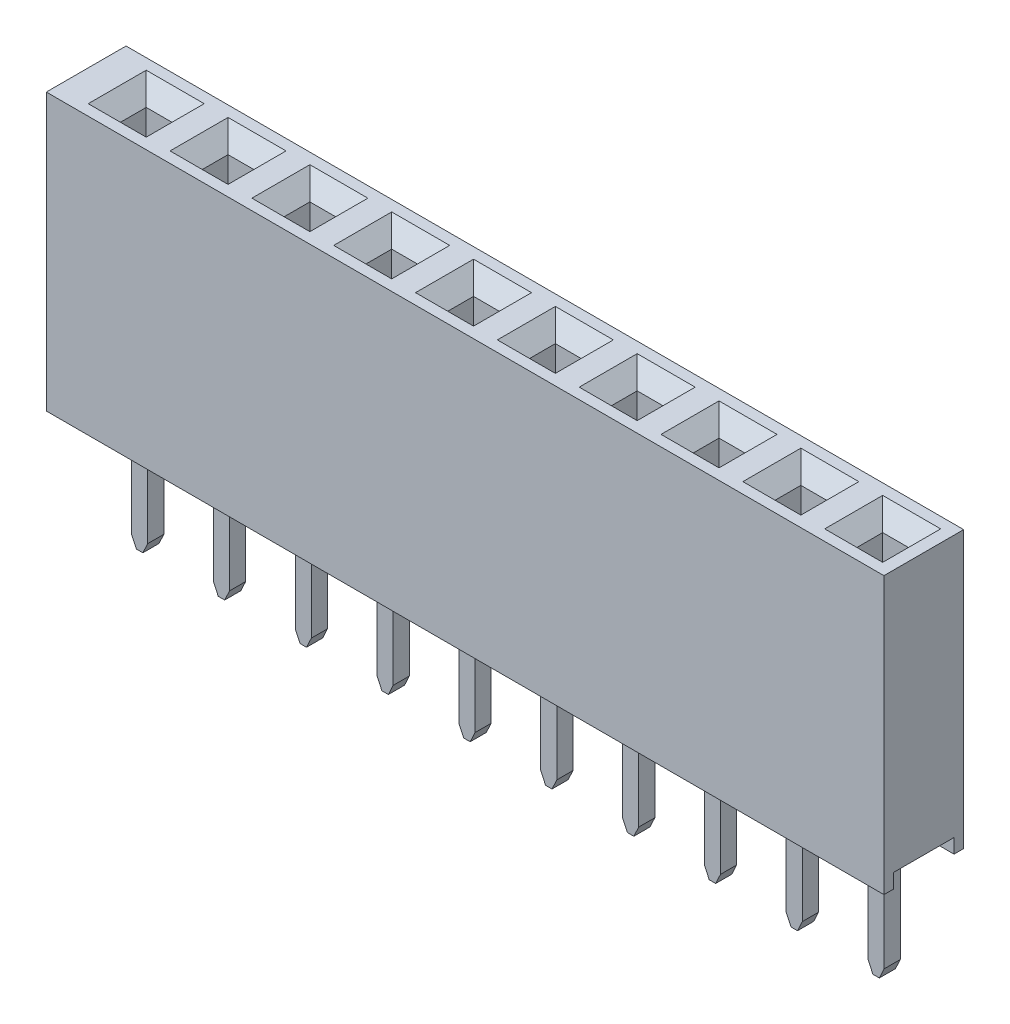
SolidWorks part; units mm, degrees
ref_plane "Front" through (0, 0, 0) normal (0, 0, 1) x (1, 0, 0)
ref_plane "Top" through (0, 0, 0) normal (0, 1, 0) x (1, 0, 0)
ref_plane "Right" through (0, 0, 0) normal (1, 0, 0) x (0, 0, -1)
sketch "Sketch1" plane through (0, 0, 0) normal (0, 0, 1) x (1, 0, 0)
  line L1 (13, -4.2875) -> (-13, -4.2875)
  line L2 (13, -4.2875) -> (13, 4.2875)
  line L3 (13, 4.2875) -> (-13, 4.2875)
  line L4 (-13, -4.2875) -> (-13, 4.2875)
  line L5 (13, -4.2875) -> (-13, 4.2875) construction
  line L6 (13, 4.2875) -> (-13, -4.2875) construction
  point P0 (0, 0)
  dimension "D1" = 26
  dimension "D2" = 8.575
extrude "Boss-Extrude1" add sketch "Sketch1" along normal mid plane 2.475
sketch "Sketch2" plane through (0, 0, 0) normal (1, 0, 0) x (0, 0, -1)
  line L0 (-0.9375, -4.2875) -> (0.9375, -4.2875)
  line L1 (-1.2375, -4.2875) -> (1.2375, -4.2875) construction
  line L2 (0.9375, -4.2875) -> (0.9375, -3.8396)
  line L3 (0.9375, -3.8396) -> (-0.9375, -3.8396)
  line L4 (-0.9375, -3.8396) -> (-0.9375, -4.2875)
  line L5 (1.2375, -4.2875) -> (1.2375, 4.2875) construction
  line L6 (-1.2375, -4.2875) -> (-1.2375, 4.2875) construction
  dimension "D1" = 0.3
  dimension "D2" = 0.3
extrude "Cut-Extrude1" cut sketch "Sketch2" against normal mid plane 100
sketch "Sketch4" plane through (0, 4.2875, 0) normal (0, 1, 0) x (1, 0, 0)
  line L0 (-13, 0) -> (13, 0) construction
  line L1 (-13, -1.2375) -> (-13, 1.2375) construction
  line L2 (13, -1.2375) -> (13, 1.2375) construction
  line L4 (-12.0116, 0.875) -> (-10.2616, 0.875)
  line L5 (-12.0116, 0.875) -> (-12.0116, -0.875)
  line L6 (-12.0116, -0.875) -> (-10.2616, -0.875)
  line L7 (-10.2616, 0.875) -> (-10.2616, -0.875)
  line L8 (-12.0116, 0.875) -> (-10.2616, -0.875) construction
  line L9 (-12.0116, -0.875) -> (-10.2616, 0.875) construction
  line L10 (-11.5366, 0.4) -> (-10.7366, 0.4)
  line L11 (-11.5366, 0.4) -> (-11.5366, -0.4)
  line L12 (-11.5366, -0.4) -> (-10.7366, -0.4)
  line L13 (-10.7366, 0.4) -> (-10.7366, -0.4)
  line L14 (-11.5366, 0.4) -> (-10.7366, -0.4) construction
  line L15 (-11.5366, -0.4) -> (-10.7366, 0.4) construction
  point P6 (-11.1366, 0)
  point P11 (-11.1366, 0)
  dimension "D1" = 1.75
  dimension "D2" = 0.8
extrude "Cut-Extrude2" cut sketch "Sketch4" against normal blind 1.5 contours L13 L10 L11 L12 region at (-11.1366, 4.2875, 0)
chamfer "Chamfer1" distance 0.5 angle 45 4 edges at (-11.1366, 4.2875, -0.4) (-11.5366, 4.2875, 0) (-11.1366, 4.2875, 0.4) (-10.7366, 4.2875, 0)
sketch "Sketch5" plane through (0, 0, 0) normal (0, 1, 0) x (1, 0, 0)
  line L1 (-12.0366, 0.9) -> (-10.2366, 0.9)
  line L2 (-12.0366, 0.9) -> (-12.0366, -0.9)
  line L3 (-12.0366, -0.9) -> (-10.2366, -0.9)
  line L4 (-10.2366, 0.9) -> (-10.2366, -0.9)
extrude "Cut-Extrude3" cut sketch "Sketch5" against normal blind 3 and the other way blind 3
sketch "Sketch9" plane through (0, 0, 0) normal (0, 0, 1) x (1, 0, 0)
  line L0 (-11.0903, 1.6344) -> (-11.0903, -6.2348) construction
  line L1 (-10.2376, -1.308) -> (-10.4881, -1.2272)
  line L2 (-10.4881, -1.2272) -> (-10.677, 1.5255)
  line L3 (-10.81, 1.373) -> (-10.5828, -1.938)
  line L4 (-10.2376, -1.308) -> (-10.2376, -2.6596)
  line L5 (-10.2376, -2.6596) -> (-10.8096, -3.0197)
  line L6 (-10.8096, -3.0197) -> (-11.371, -3.0197)
  line L7 (-11.9431, -2.6596) -> (-11.371, -3.0197)
  line L8 (-11.9431, -1.308) -> (-11.9431, -2.6596)
  line L9 (-11.9431, -1.308) -> (-11.6925, -1.2272)
  line L10 (-11.6925, -1.2272) -> (-11.5036, 1.5255)
  line L11 (-11.3706, 1.373) -> (-11.5978, -1.938)
  line L12 (-11.1903, -7.5875) -> (-10.9903, -7.5875)
  line L13 (-10.9903, -7.5875) -> (-10.8403, -7.2658)
  line L14 (-10.8403, -7.2658) -> (-10.8403, -3.0197)
  line L15 (-11.1903, -7.5875) -> (-11.3403, -7.2658)
  line L16 (-11.3403, -7.2658) -> (-11.3403, -3.0197)
  line L17 (-13, -4.2875) -> (13, -4.2875) construction
  arc A0 (-10.677, 1.5255) -> (-10.81, 1.373) centre (-10.8198, 1.5157) ccw
  arc A1 (-10.5828, -1.938) -> (-11.0903, -2.3606) centre (-10.9893, -1.9659) cw
  arc A2 (-11.5978, -1.938) -> (-11.0903, -2.3606) centre (-11.1914, -1.9659) ccw
  arc A3 (-11.5036, 1.5255) -> (-11.3706, 1.373) centre (-11.3608, 1.5157) cw
  point P16 (-11.0903, -3.0197)
  point P24 (-11.3403, -4.2875)
  dimension "D1" = 115
  dimension "D2" = 115
  dimension "D3" = 0.25
  dimension "D4" = 0.2
  dimension "D5" = 0.25
  dimension "D6" = 3.3
extrude "Boss-Extrude4" add sketch "Sketch9" along normal mid plane 1.7 contours A1 L0 L6 L5 L4 L1 L2 A0 L3 | L0 A2 L11 A3 L10 L9 L8 L7 L6 region at (-10.6123, -1.401, 0) region at (-11.5683, -1.401, 0)
extrude "Boss-Extrude5" add sketch "Sketch9<3>" along normal mid plane 0.5 contours L16 L15 L12 L13 L14 L6 region at (-11.0903, -5.2566, 0)
sketch "Sketch9<3>" plane through (0, 0, 0) normal (0, 0, 1) x (1, 0, 0) same geometry as "Sketch9"
pattern_linear "LPattern1" count 10 spacing 2.54 along (1, 0, 0) of "Chamfer1", "Cut-Extrude3", "Boss-Extrude4", "Boss-Extrude5", "Cut-Extrude2"
